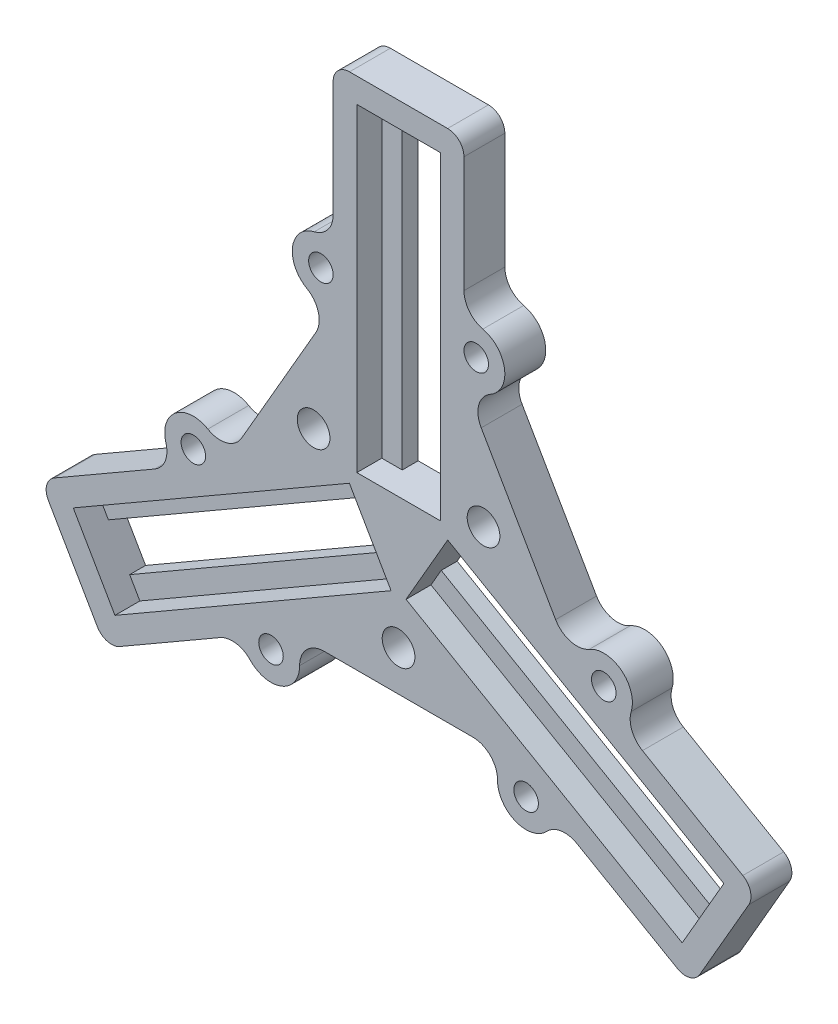
SolidWorks part; units mm, degrees
ref_plane "Front Plane" through (0, 0, 0) normal (0, 0, 1) x (1, 0, 0)
ref_plane "Top Plane" through (0, 0, 0) normal (0, 1, 0) x (1, 0, 0)
ref_plane "Right Plane" through (0, 0, 0) normal (1, 0, 0) x (0, 0, -1)
sketch "Sketch1" plane through (0, 0, 0) normal (0, 0, 1) x (1, 0, 0)
  line L0 (0, 0) -> (0, 23.5) construction
  line L1 (4.7641, 0.2517) -> (2.1641, -4.2517)
  line L2 (-2.6, 43) -> (2.6, 43)
  line L3 (-2.6, 43) -> (-2.6, 4)
  line L4 (-2.6, 4) -> (2.6, 4)
  line L5 (2.6, 43) -> (2.6, 4)
  line L6 (-2.6, 43) -> (2.6, 4) construction
  line L7 (-2.6, 4) -> (2.6, 43) construction
  line L8 (35.9391, -23.7517) -> (2.1641, -4.2517)
  line L9 (38.5391, -19.2483) -> (4.7641, 0.2517)
  line L10 (38.5391, -19.2483) -> (35.9391, -23.7517)
  line L11 (-2.1641, -4.2517) -> (-4.7641, 0.2517)
  line L12 (-38.5391, -19.2483) -> (-4.7641, 0.2517)
  line L13 (-35.9391, -23.7517) -> (-2.1641, -4.2517)
  line L14 (-35.9391, -23.7517) -> (-38.5391, -19.2483)
  line L15 (2.6, 4) -> (2.6, 1) construction
  line L16 (4.7641, 0.2517) -> (2.166, 1.7517) construction
  line L17 (0, 23.5) -> (0, 43) construction
  line L18 (21.3205, -3.0718) -> (13.3205, -16.9282) construction
  line L19 (-8, 46) -> (8, 46)
  line L20 (-8, 46) -> (-8, 20)
  line L21 (-8, 20) -> (8, 20) construction
  line L22 (8, 46) -> (8, 20)
  line L23 (-8, 46) -> (8, 20) construction
  line L24 (-8, 20) -> (8, 46) construction
  line L25 (43.8372, -16.0718) -> (21.3205, -3.0718)
  line L26 (35.8372, -29.9282) -> (13.3205, -16.9282)
  line L27 (43.8372, -16.0718) -> (35.8372, -29.9282)
  line L28 (-13.3205, -16.9282) -> (-21.3205, -3.0718) construction
  line L29 (-35.8372, -29.9282) -> (-13.3205, -16.9282)
  line L30 (-43.8372, -16.0718) -> (-21.3205, -3.0718)
  line L31 (-35.8372, -29.9282) -> (-43.8372, -16.0718)
  line L32 (8, 20) -> (21.3205, -3.0718)
  line L33 (-8, 20) -> (-21.3205, -3.0718)
  line L34 (-13.3205, -16.9282) -> (13.3205, -16.9282)
  circle A0 centre (0, 0) radius 45.1165 construction
  point P3 (0, 23.5)
  point P9 (0, 33)
  point P20 (0, 0)
  point P37 (0, 0)
  dimension "D3" = 3
  dimension "D1" = 5.2
  dimension "D2" = 39
  dimension "D4" = 3
  dimension "D5" = 3
  dimension "D6" = 4
  dimension "D8" = 16
  dimension "D9" = 3
  dimension "D10" = 20
  dimension "D7" = 3
extrude "Boss-Extrude1" add sketch "Sketch1" along normal blind 5
sketch "Sketch2" plane through (0, 0, 5) normal (0, 0, 1) x (1, 0, 0)
  line L0 (-2.6, 4) -> (2.6, 4) construction
  line L1 (-5.1, 43) -> (5.1, 43)
  line L2 (-5.1, 43) -> (-5.1, 4)
  line L3 (-5.1, 4) -> (5.1, 4)
  line L4 (5.1, 43) -> (5.1, 4)
  line L5 (2.6, 43) -> (-2.6, 43) construction
  line L6 (2.6, 4) -> (2.6, 43) construction
  line L7 (-2.6, 43) -> (-2.6, 4) construction
  line L8 (39.7891, -17.0833) -> (34.6891, -25.9167)
  line L9 (39.7891, -17.0833) -> (6.0141, 2.4167)
  line L10 (6.0141, 2.4167) -> (0.9141, -6.4167)
  line L11 (34.6891, -25.9167) -> (0.9141, -6.4167)
  line L12 (-34.6891, -25.9167) -> (-39.7891, -17.0833)
  line L13 (-34.6891, -25.9167) -> (-0.9141, -6.4167)
  line L14 (-0.9141, -6.4167) -> (-6.0141, 2.4167)
  line L15 (-39.7891, -17.0833) -> (-6.0141, 2.4167)
  point P23 (0, 0)
  dimension "D1" = 2.5
  dimension "D2" = 2.5
  dimension "D3" = 3
extrude "Cut-Extrude1" cut sketch "Sketch2" against normal blind 3.05
sketch "Sketch3" plane through (0, 0, 5) normal (0, 0, 1) x (1, 0, 0)
  line L0 (0, 0) -> (0, -12) construction
  circle A0 centre (0, -12) radius 2
  circle A1 centre (-10.3923, 6) radius 2
  circle A2 centre (10.3923, 6) radius 2
  point P11 (0, 0)
  dimension "D1" = 4
  dimension "D2" = 12
  dimension "D3" = 3
extrude "Cut-Extrude2" cut sketch "Sketch3" against normal up to next
sketch "Sketch4" plane through (0, 0, 5) normal (0, 0, 1) x (1, 0, 0)
  line L0 (5.1, 23.5) -> (10.7719, 23.5) construction
  line L1 (5.1, 4) -> (5.1, 43) construction
  line L2 (8, 20) -> (8, 46) construction
  line L3 (0, 0) -> (0, 32.8851) construction
  line L4 (-5.1, 23.5) -> (-10.7719, 23.5) construction
  circle A0 centre (9.5, 23.5) radius 1.5
  circle A1 centre (9.5, 23.5) radius 3.5
  circle A2 centre (-9.5, 23.5) radius 3.5
  circle A3 centre (-9.5, 23.5) radius 1.5
  circle A4 centre (25.1016, -3.5228) radius 3.5
  circle A5 centre (25.1016, -3.5228) radius 1.5
  circle A6 centre (15.6016, -19.9772) radius 3.5
  circle A7 centre (15.6016, -19.9772) radius 1.5
  circle A8 centre (-15.6016, -19.9772) radius 3.5
  circle A9 centre (-15.6016, -19.9772) radius 1.5
  circle A10 centre (-25.1016, -3.5228) radius 3.5
  circle A11 centre (-25.1016, -3.5228) radius 1.5
  point P32 (0, 0)
  dimension "D1" = 3
  dimension "D2" = 7
  dimension "D3" = 3
extrude "Boss-Extrude2" add sketch "Sketch4" against normal up to surface (5 mm away) up to face at (2, -12, 0)
fillet "Fillet1" radius 3 12 edges at (21.613, -3.2407, 2.5) (27.0902, -6.4029, 2.5) (13.613, -17.0971, 2.5) (19.0902, -20.2593, 2.5) (-13.613, -17.0971, 2.5) (-19.0902, -20.2593, 2.5) (-21.613, -3.2407, 2.5) (-27.0902, -6.4029, 2.5) (8, 26.6623, 2.5) (8, 20.3377, 2.5) (-8, 20.3377, 2.5) (-8, 26.6623, 2.5)
fillet "Fillet2" radius 3 6 edges at (8, 20, 2.5) (-8, 20, 2.5) (-21.3205, -3.0718, 2.5) (-13.3205, -16.9282, 2.5) (13.3205, -16.9282, 2.5) (21.3205, -3.0718, 2.5)
fillet "Fillet3" radius 2 6 edges at (-43.8372, -16.0718, 2.5) (-35.8372, -29.9282, 2.5) (35.8372, -29.9282, 2.5) (43.8372, -16.0718, 2.5) (-8, 46, 2.5) (8, 46, 2.5)
